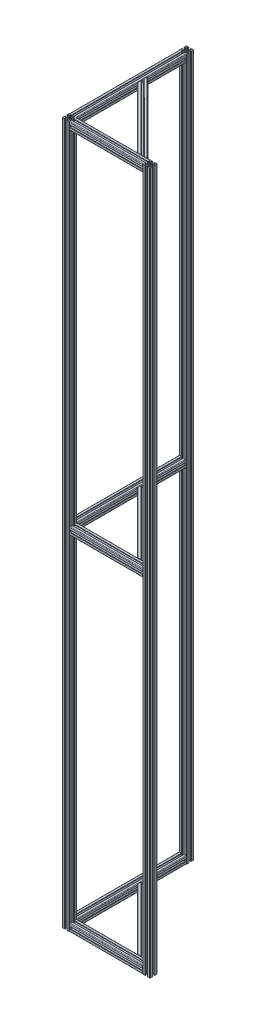
SolidWorks part; units mm, degrees
ref_plane "Front Plane" through (0, 0, 0) normal (0, 0, 1) x (1, 0, 0)
ref_plane "Top Plane" through (0, 0, 0) normal (0, 1, 0) x (1, 0, 0)
ref_plane "Right Plane" through (0, 0, 0) normal (1, 0, 0) x (0, 0, -1)
sketch "Sketch1" plane through (0, 0, 0) normal (0, 1, 0) x (1, 0, 0)
  line L0 (0, 0) -> (0, 406.4)
  line L1 (0, 0) -> (279.4, 0)
  line L2 (0, 254) -> (254, 0)
  point P6 (0, 0)
  point P7 (0, 0)
  dimension "D1" = 90
  dimension "D2" = 406.4
  dimension "D3" = 279.4
  dimension "D4" = 45
  dimension "D5" = 254
ref_plane "Plane1" through (0, 787.4, 0) normal (0, 1, 0) x (1, 0, 0)
sketch "Sketch2" plane through (0, 787.4, 0) normal (0, 1, 0) x (1, 0, 0)
  line L0 (0, 254) -> (254, 0) construction
  line L1 (0, 0) -> (0, 406.4) construction
  line L2 (0, 0) -> (279.4, 0) construction
  line L3 (0, 254) -> (254, 0)
  line L4 (0, 0) -> (0, 406.4)
  line L5 (0, 0) -> (279.4, 0)
ref_plane "Plane2" through (0, 1193.8, 0) normal (0, 1, 0) x (1, 0, 0)
sketch "Sketch3" plane through (0, 1193.8, 0) normal (0, 1, 0) x (1, 0, 0)
  line L0 (0, 254) -> (254, 0) construction
  line L1 (0, 0) -> (0, 406.4) construction
  line L2 (0, 0) -> (279.4, 0) construction
  line L3 (0, 254) -> (254, 0)
  line L4 (0, 0) -> (0, 406.4)
  line L5 (0, 0) -> (279.4, 0)
ref_plane "Plane3" through (0, 2413, 0) normal (0, 1, 0) x (1, 0, 0)
sketch "Sketch4" plane through (0, 2413, 0) normal (0, 1, 0) x (1, 0, 0)
  line L0 (0, 254) -> (254, 0) construction
  line L1 (0, 0) -> (0, 406.4) construction
  line L2 (0, 0) -> (279.4, 0) construction
  line L3 (0, 254) -> (254, 0)
  line L4 (0, 0) -> (0, 406.4)
  line L5 (0, 0) -> (279.4, 0)
sketch3d "3DSketch1"
  line L0 (0, 0, 0) -> (0, 2413, 0)
  line L1 (279.4, 0, 0) -> (279.4, 2413, 0)
  line L2 (0, 2413, -406.4) -> (0, 0, -406.4)
other "8020 1010-S(1)"
ref_plane "Plane4" through (279.4, 0, 0) normal (0, 1, 0) x (1, 0, 0)
sketch "Sketch11" plane through (279.4, 0, 0) normal (0, 1, 0) x (1, 0, 0)
  line L0 (-2.8605, -1.9692) -> (-2.2319, -1.3405)
  line L1 (-2.2319, 1.3405) -> (-2.8605, 1.9692)
  line L2 (-1.9692, 2.8605) -> (-1.3405, 2.2319)
  line L3 (1.3405, 2.2319) -> (1.9692, 2.8605)
  line L4 (2.8605, 1.9692) -> (2.2319, 1.3405)
  line L5 (2.2319, -1.3405) -> (2.8605, -1.9692)
  line L6 (1.9692, -2.8605) -> (1.3405, -2.2319)
  line L7 (-1.3405, -2.2319) -> (-1.9692, -2.8605)
  line L8 (-3.8846, 5.4471) -> (-7.1933, 8.7558)
  line L9 (1.6396, 4.5172) -> (-1.6396, 4.5172)
  line L10 (7.1933, 8.7558) -> (3.8846, 5.4471)
  line L11 (12.7, -10.5918) -> (12.7, -4.3561)
  line L12 (5.4471, 3.8846) -> (8.7558, 7.1933)
  line L13 (4.5172, -1.6396) -> (4.5172, 1.6396)
  line L14 (8.7558, -7.1933) -> (5.4471, -3.8846)
  line L15 (-10.5918, -12.7) -> (-4.3561, -12.7)
  line L16 (3.8846, -5.4471) -> (7.1933, -8.7558)
  line L17 (-1.6396, -4.5172) -> (1.6396, -4.5172)
  line L18 (-7.1933, -8.7558) -> (-3.8846, -5.4471)
  line L19 (-12.7, 10.5918) -> (-12.7, 4.3561)
  line L20 (-5.4471, -3.8846) -> (-8.7558, -7.1933)
  line L21 (-4.5172, 1.6396) -> (-4.5172, -1.6396)
  line L22 (-8.7558, 7.1933) -> (-5.4471, 3.8846)
  line L23 (-10.5918, 12.7) -> (-4.3561, 12.7)
  line L24 (-6.4749, 10.4902) -> (-4.3561, 10.4902)
  line L25 (-10.4902, 6.4749) -> (-10.4902, 4.3561)
  line L26 (-6.4749, -10.4902) -> (-4.3561, -10.4902)
  line L27 (10.4902, -6.4749) -> (10.4902, -4.3561)
  line L28 (4.3561, 12.7) -> (10.5918, 12.7)
  line L29 (4.3561, 10.4902) -> (6.4749, 10.4902)
  line L30 (-10.4902, -4.3561) -> (-10.4902, -6.4749)
  line L31 (-12.7, -4.3561) -> (-12.7, -10.5918)
  line L32 (4.3561, -10.4902) -> (6.4749, -10.4902)
  line L33 (4.3561, -12.7) -> (10.5918, -12.7)
  line L34 (12.7, 4.3561) -> (12.7, 10.5918)
  line L35 (10.4902, 4.3561) -> (10.4902, 6.4749)
  arc A0 (-2.8605, -1.9692) -> (-1.9692, -2.8605) centre (-2.4696, -2.4696) ccw
  arc A1 (-2.2319, 1.3405) -> (-2.2319, -1.3405) centre (0, 0) ccw
  arc A2 (-1.9692, 2.8605) -> (-2.8605, 1.9692) centre (-2.4696, 2.4696) ccw
  arc A3 (1.3405, 2.2319) -> (-1.3405, 2.2319) centre (0, 0) ccw
  arc A4 (2.8605, 1.9692) -> (1.9692, 2.8605) centre (2.4696, 2.4696) ccw
  arc A5 (2.2319, -1.3405) -> (2.2319, 1.3405) centre (0, 0) ccw
  arc A6 (1.9692, -2.8605) -> (2.8605, -1.9692) centre (2.4696, -2.4696) ccw
  arc A7 (-1.3405, -2.2319) -> (1.3405, -2.2319) centre (0, 0) ccw
  arc A8 (-3.8846, 5.4471) -> (-1.6396, 4.5172) centre (-1.6396, 7.6922) ccw
  arc A9 (1.6396, 4.5172) -> (3.8846, 5.4471) centre (1.6396, 7.6922) ccw
  arc A10 (5.4471, 3.8846) -> (4.5172, 1.6396) centre (7.6922, 1.6396) ccw
  arc A11 (4.5172, -1.6396) -> (5.4471, -3.8846) centre (7.6922, -1.6396) ccw
  arc A12 (3.8846, -5.4471) -> (1.6396, -4.5172) centre (1.6396, -7.6922) ccw
  arc A13 (-1.6396, -4.5172) -> (-3.8846, -5.4471) centre (-1.6396, -7.6922) ccw
  arc A14 (-5.4471, -3.8846) -> (-4.5172, -1.6396) centre (-7.6922, -1.6396) ccw
  arc A15 (-4.5172, 1.6396) -> (-5.4471, 3.8846) centre (-7.6922, 1.6396) ccw
  arc A16 (-12.7, -10.5918) -> (-10.5918, -12.7) centre (-10.5918, -10.5918) ccw
  arc A17 (10.5918, -12.7) -> (12.7, -10.5918) centre (10.5918, -10.5918) ccw
  arc A18 (12.7, 10.5918) -> (10.5918, 12.7) centre (10.5918, 10.5918) ccw
  arc A19 (-10.5918, 12.7) -> (-12.7, 10.5918) centre (-10.5918, 10.5918) ccw
  arc A20 (-8.7558, 7.1933) -> (-10.4902, 6.4749) centre (-9.4742, 6.4749) ccw
  arc A21 (-6.4749, 10.4902) -> (-7.1933, 8.7558) centre (-6.4749, 9.4742) ccw
  arc A22 (7.1933, 8.7558) -> (6.4749, 10.4902) centre (6.4749, 9.4742) ccw
  arc A23 (10.4902, 6.4749) -> (8.7558, 7.1933) centre (9.4742, 6.4749) ccw
  arc A24 (8.7558, -7.1933) -> (10.4902, -6.4749) centre (9.4742, -6.4749) ccw
  arc A25 (6.4749, -10.4902) -> (7.1933, -8.7558) centre (6.4749, -9.4742) ccw
  arc A26 (-7.1933, -8.7558) -> (-6.4749, -10.4902) centre (-6.4749, -9.4742) ccw
  arc A27 (-10.4902, -6.4749) -> (-8.7558, -7.1933) centre (-9.4742, -6.4749) ccw
  arc A28 (-4.3561, 10.4902) -> (-4.3561, 12.7) centre (-4.3561, 11.5951) ccw
  arc A29 (4.3561, 12.7) -> (4.3561, 10.4902) centre (4.3561, 11.5951) ccw
  arc A30 (-12.7, 4.3561) -> (-10.4902, 4.3561) centre (-11.5951, 4.3561) ccw
  arc A31 (-10.4902, -4.3561) -> (-12.7, -4.3561) centre (-11.5951, -4.3561) ccw
  arc A32 (-4.3561, -12.7) -> (-4.3561, -10.4902) centre (-4.3561, -11.5951) ccw
  arc A33 (4.3561, -10.4902) -> (4.3561, -12.7) centre (4.3561, -11.5951) ccw
  arc A34 (12.7, -4.3561) -> (10.4902, -4.3561) centre (11.5951, -4.3561) ccw
  arc A35 (10.4902, 4.3561) -> (12.7, 4.3561) centre (11.5951, 4.3561) ccw
  point P0 (0, 0)
other "8020 1010-S(2)"
ref_plane "Plane5" through (0, 2413, 0) normal (1, 0, 0) x (0, 0, -1)
sketch "Sketch12" plane through (0, 2413, 0) normal (1, 0, 0) x (0, 0, -1)
  line L0 (-2.8605, -1.9692) -> (-2.2319, -1.3405)
  line L1 (-2.2319, 1.3405) -> (-2.8605, 1.9692)
  line L2 (-1.9692, 2.8605) -> (-1.3405, 2.2319)
  line L3 (1.3405, 2.2319) -> (1.9692, 2.8605)
  line L4 (2.8605, 1.9692) -> (2.2319, 1.3405)
  line L5 (2.2319, -1.3405) -> (2.8605, -1.9692)
  line L6 (1.9692, -2.8605) -> (1.3405, -2.2319)
  line L7 (-1.3405, -2.2319) -> (-1.9692, -2.8605)
  line L8 (-3.8846, 5.4471) -> (-7.1933, 8.7558)
  line L9 (1.6396, 4.5172) -> (-1.6396, 4.5172)
  line L10 (7.1933, 8.7558) -> (3.8846, 5.4471)
  line L11 (12.7, -10.5918) -> (12.7, -4.3561)
  line L12 (5.4471, 3.8846) -> (8.7558, 7.1933)
  line L13 (4.5172, -1.6396) -> (4.5172, 1.6396)
  line L14 (8.7558, -7.1933) -> (5.4471, -3.8846)
  line L15 (-10.5918, -12.7) -> (-4.3561, -12.7)
  line L16 (3.8846, -5.4471) -> (7.1933, -8.7558)
  line L17 (-1.6396, -4.5172) -> (1.6396, -4.5172)
  line L18 (-7.1933, -8.7558) -> (-3.8846, -5.4471)
  line L19 (-12.7, 10.5918) -> (-12.7, 4.3561)
  line L20 (-5.4471, -3.8846) -> (-8.7558, -7.1933)
  line L21 (-4.5172, 1.6396) -> (-4.5172, -1.6396)
  line L22 (-8.7558, 7.1933) -> (-5.4471, 3.8846)
  line L23 (-10.5918, 12.7) -> (-4.3561, 12.7)
  line L24 (-6.4749, 10.4902) -> (-4.3561, 10.4902)
  line L25 (-10.4902, 6.4749) -> (-10.4902, 4.3561)
  line L26 (-6.4749, -10.4902) -> (-4.3561, -10.4902)
  line L27 (10.4902, -6.4749) -> (10.4902, -4.3561)
  line L28 (4.3561, 12.7) -> (10.5918, 12.7)
  line L29 (4.3561, 10.4902) -> (6.4749, 10.4902)
  line L30 (-10.4902, -4.3561) -> (-10.4902, -6.4749)
  line L31 (-12.7, -4.3561) -> (-12.7, -10.5918)
  line L32 (4.3561, -10.4902) -> (6.4749, -10.4902)
  line L33 (4.3561, -12.7) -> (10.5918, -12.7)
  line L34 (12.7, 4.3561) -> (12.7, 10.5918)
  line L35 (10.4902, 4.3561) -> (10.4902, 6.4749)
  arc A0 (-2.8605, -1.9692) -> (-1.9692, -2.8605) centre (-2.4696, -2.4696) ccw
  arc A1 (-2.2319, 1.3405) -> (-2.2319, -1.3405) centre (0, 0) ccw
  arc A2 (-1.9692, 2.8605) -> (-2.8605, 1.9692) centre (-2.4696, 2.4696) ccw
  arc A3 (1.3405, 2.2319) -> (-1.3405, 2.2319) centre (0, 0) ccw
  arc A4 (2.8605, 1.9692) -> (1.9692, 2.8605) centre (2.4696, 2.4696) ccw
  arc A5 (2.2319, -1.3405) -> (2.2319, 1.3405) centre (0, 0) ccw
  arc A6 (1.9692, -2.8605) -> (2.8605, -1.9692) centre (2.4696, -2.4696) ccw
  arc A7 (-1.3405, -2.2319) -> (1.3405, -2.2319) centre (0, 0) ccw
  arc A8 (-3.8846, 5.4471) -> (-1.6396, 4.5172) centre (-1.6396, 7.6922) ccw
  arc A9 (1.6396, 4.5172) -> (3.8846, 5.4471) centre (1.6396, 7.6922) ccw
  arc A10 (5.4471, 3.8846) -> (4.5172, 1.6396) centre (7.6922, 1.6396) ccw
  arc A11 (4.5172, -1.6396) -> (5.4471, -3.8846) centre (7.6922, -1.6396) ccw
  arc A12 (3.8846, -5.4471) -> (1.6396, -4.5172) centre (1.6396, -7.6922) ccw
  arc A13 (-1.6396, -4.5172) -> (-3.8846, -5.4471) centre (-1.6396, -7.6922) ccw
  arc A14 (-5.4471, -3.8846) -> (-4.5172, -1.6396) centre (-7.6922, -1.6396) ccw
  arc A15 (-4.5172, 1.6396) -> (-5.4471, 3.8846) centre (-7.6922, 1.6396) ccw
  arc A16 (-12.7, -10.5918) -> (-10.5918, -12.7) centre (-10.5918, -10.5918) ccw
  arc A17 (10.5918, -12.7) -> (12.7, -10.5918) centre (10.5918, -10.5918) ccw
  arc A18 (12.7, 10.5918) -> (10.5918, 12.7) centre (10.5918, 10.5918) ccw
  arc A19 (-10.5918, 12.7) -> (-12.7, 10.5918) centre (-10.5918, 10.5918) ccw
  arc A20 (-8.7558, 7.1933) -> (-10.4902, 6.4749) centre (-9.4742, 6.4749) ccw
  arc A21 (-6.4749, 10.4902) -> (-7.1933, 8.7558) centre (-6.4749, 9.4742) ccw
  arc A22 (7.1933, 8.7558) -> (6.4749, 10.4902) centre (6.4749, 9.4742) ccw
  arc A23 (10.4902, 6.4749) -> (8.7558, 7.1933) centre (9.4742, 6.4749) ccw
  arc A24 (8.7558, -7.1933) -> (10.4902, -6.4749) centre (9.4742, -6.4749) ccw
  arc A25 (6.4749, -10.4902) -> (7.1933, -8.7558) centre (6.4749, -9.4742) ccw
  arc A26 (-7.1933, -8.7558) -> (-6.4749, -10.4902) centre (-6.4749, -9.4742) ccw
  arc A27 (-10.4902, -6.4749) -> (-8.7558, -7.1933) centre (-9.4742, -6.4749) ccw
  arc A28 (-4.3561, 10.4902) -> (-4.3561, 12.7) centre (-4.3561, 11.5951) ccw
  arc A29 (4.3561, 12.7) -> (4.3561, 10.4902) centre (4.3561, 11.5951) ccw
  arc A30 (-12.7, 4.3561) -> (-10.4902, 4.3561) centre (-11.5951, 4.3561) ccw
  arc A31 (-10.4902, -4.3561) -> (-12.7, -4.3561) centre (-11.5951, -4.3561) ccw
  arc A32 (-4.3561, -12.7) -> (-4.3561, -10.4902) centre (-4.3561, -11.5951) ccw
  arc A33 (4.3561, -10.4902) -> (4.3561, -12.7) centre (4.3561, -11.5951) ccw
  arc A34 (12.7, -4.3561) -> (10.4902, -4.3561) centre (11.5951, -4.3561) ccw
  arc A35 (10.4902, 4.3561) -> (12.7, 4.3561) centre (11.5951, 4.3561) ccw
  point P0 (0, 0)
other "8020 1010-S(3)"
ref_plane "Plane6" through (0, 2413, 0) normal (0, 0, -1) x (-1, 0, 0)
sketch "Sketch13" plane through (0, 2413, 0) normal (0, 0, -1) x (-1, 0, 0)
  line L0 (-2.8605, -1.9692) -> (-2.2319, -1.3405)
  line L1 (-2.2319, 1.3405) -> (-2.8605, 1.9692)
  line L2 (-1.9692, 2.8605) -> (-1.3405, 2.2319)
  line L3 (1.3405, 2.2319) -> (1.9692, 2.8605)
  line L4 (2.8605, 1.9692) -> (2.2319, 1.3405)
  line L5 (2.2319, -1.3405) -> (2.8605, -1.9692)
  line L6 (1.9692, -2.8605) -> (1.3405, -2.2319)
  line L7 (-1.3405, -2.2319) -> (-1.9692, -2.8605)
  line L8 (-3.8846, 5.4471) -> (-7.1933, 8.7558)
  line L9 (1.6396, 4.5172) -> (-1.6396, 4.5172)
  line L10 (7.1933, 8.7558) -> (3.8846, 5.4471)
  line L11 (12.7, -10.5918) -> (12.7, -4.3561)
  line L12 (5.4471, 3.8846) -> (8.7558, 7.1933)
  line L13 (4.5172, -1.6396) -> (4.5172, 1.6396)
  line L14 (8.7558, -7.1933) -> (5.4471, -3.8846)
  line L15 (-10.5918, -12.7) -> (-4.3561, -12.7)
  line L16 (3.8846, -5.4471) -> (7.1933, -8.7558)
  line L17 (-1.6396, -4.5172) -> (1.6396, -4.5172)
  line L18 (-7.1933, -8.7558) -> (-3.8846, -5.4471)
  line L19 (-12.7, 10.5918) -> (-12.7, 4.3561)
  line L20 (-5.4471, -3.8846) -> (-8.7558, -7.1933)
  line L21 (-4.5172, 1.6396) -> (-4.5172, -1.6396)
  line L22 (-8.7558, 7.1933) -> (-5.4471, 3.8846)
  line L23 (-10.5918, 12.7) -> (-4.3561, 12.7)
  line L24 (-6.4749, 10.4902) -> (-4.3561, 10.4902)
  line L25 (-10.4902, 6.4749) -> (-10.4902, 4.3561)
  line L26 (-6.4749, -10.4902) -> (-4.3561, -10.4902)
  line L27 (10.4902, -6.4749) -> (10.4902, -4.3561)
  line L28 (4.3561, 12.7) -> (10.5918, 12.7)
  line L29 (4.3561, 10.4902) -> (6.4749, 10.4902)
  line L30 (-10.4902, -4.3561) -> (-10.4902, -6.4749)
  line L31 (-12.7, -4.3561) -> (-12.7, -10.5918)
  line L32 (4.3561, -10.4902) -> (6.4749, -10.4902)
  line L33 (4.3561, -12.7) -> (10.5918, -12.7)
  line L34 (12.7, 4.3561) -> (12.7, 10.5918)
  line L35 (10.4902, 4.3561) -> (10.4902, 6.4749)
  arc A0 (-2.8605, -1.9692) -> (-1.9692, -2.8605) centre (-2.4696, -2.4696) ccw
  arc A1 (-2.2319, 1.3405) -> (-2.2319, -1.3405) centre (0, 0) ccw
  arc A2 (-1.9692, 2.8605) -> (-2.8605, 1.9692) centre (-2.4696, 2.4696) ccw
  arc A3 (1.3405, 2.2319) -> (-1.3405, 2.2319) centre (0, 0) ccw
  arc A4 (2.8605, 1.9692) -> (1.9692, 2.8605) centre (2.4696, 2.4696) ccw
  arc A5 (2.2319, -1.3405) -> (2.2319, 1.3405) centre (0, 0) ccw
  arc A6 (1.9692, -2.8605) -> (2.8605, -1.9692) centre (2.4696, -2.4696) ccw
  arc A7 (-1.3405, -2.2319) -> (1.3405, -2.2319) centre (0, 0) ccw
  arc A8 (-3.8846, 5.4471) -> (-1.6396, 4.5172) centre (-1.6396, 7.6922) ccw
  arc A9 (1.6396, 4.5172) -> (3.8846, 5.4471) centre (1.6396, 7.6922) ccw
  arc A10 (5.4471, 3.8846) -> (4.5172, 1.6396) centre (7.6922, 1.6396) ccw
  arc A11 (4.5172, -1.6396) -> (5.4471, -3.8846) centre (7.6922, -1.6396) ccw
  arc A12 (3.8846, -5.4471) -> (1.6396, -4.5172) centre (1.6396, -7.6922) ccw
  arc A13 (-1.6396, -4.5172) -> (-3.8846, -5.4471) centre (-1.6396, -7.6922) ccw
  arc A14 (-5.4471, -3.8846) -> (-4.5172, -1.6396) centre (-7.6922, -1.6396) ccw
  arc A15 (-4.5172, 1.6396) -> (-5.4471, 3.8846) centre (-7.6922, 1.6396) ccw
  arc A16 (-12.7, -10.5918) -> (-10.5918, -12.7) centre (-10.5918, -10.5918) ccw
  arc A17 (10.5918, -12.7) -> (12.7, -10.5918) centre (10.5918, -10.5918) ccw
  arc A18 (12.7, 10.5918) -> (10.5918, 12.7) centre (10.5918, 10.5918) ccw
  arc A19 (-10.5918, 12.7) -> (-12.7, 10.5918) centre (-10.5918, 10.5918) ccw
  arc A20 (-8.7558, 7.1933) -> (-10.4902, 6.4749) centre (-9.4742, 6.4749) ccw
  arc A21 (-6.4749, 10.4902) -> (-7.1933, 8.7558) centre (-6.4749, 9.4742) ccw
  arc A22 (7.1933, 8.7558) -> (6.4749, 10.4902) centre (6.4749, 9.4742) ccw
  arc A23 (10.4902, 6.4749) -> (8.7558, 7.1933) centre (9.4742, 6.4749) ccw
  arc A24 (8.7558, -7.1933) -> (10.4902, -6.4749) centre (9.4742, -6.4749) ccw
  arc A25 (6.4749, -10.4902) -> (7.1933, -8.7558) centre (6.4749, -9.4742) ccw
  arc A26 (-7.1933, -8.7558) -> (-6.4749, -10.4902) centre (-6.4749, -9.4742) ccw
  arc A27 (-10.4902, -6.4749) -> (-8.7558, -7.1933) centre (-9.4742, -6.4749) ccw
  arc A28 (-4.3561, 10.4902) -> (-4.3561, 12.7) centre (-4.3561, 11.5951) ccw
  arc A29 (4.3561, 12.7) -> (4.3561, 10.4902) centre (4.3561, 11.5951) ccw
  arc A30 (-12.7, 4.3561) -> (-10.4902, 4.3561) centre (-11.5951, 4.3561) ccw
  arc A31 (-10.4902, -4.3561) -> (-12.7, -4.3561) centre (-11.5951, -4.3561) ccw
  arc A32 (-4.3561, -12.7) -> (-4.3561, -10.4902) centre (-4.3561, -11.5951) ccw
  arc A33 (4.3561, -10.4902) -> (4.3561, -12.7) centre (4.3561, -11.5951) ccw
  arc A34 (12.7, -4.3561) -> (10.4902, -4.3561) centre (11.5951, -4.3561) ccw
  arc A35 (10.4902, 4.3561) -> (12.7, 4.3561) centre (11.5951, 4.3561) ccw
  point P0 (0, 0)
other "8020 1010-S(4)"
ref_plane "Plane7" through (0, 2413, -254) normal (0.7071, 0, 0.7071) x (0.7071, 0, -0.7071)
sketch "Sketch14" plane through (0, 2413, -254) normal (0.7071, 0, 0.7071) x (0.7071, 0, -0.7071)
  line L0 (-2.8605, -1.9692) -> (-2.2319, -1.3405)
  line L1 (-2.2319, 1.3405) -> (-2.8605, 1.9692)
  line L2 (-1.9692, 2.8605) -> (-1.3405, 2.2319)
  line L3 (1.3405, 2.2319) -> (1.9692, 2.8605)
  line L4 (2.8605, 1.9692) -> (2.2319, 1.3405)
  line L5 (2.2319, -1.3405) -> (2.8605, -1.9692)
  line L6 (1.9692, -2.8605) -> (1.3405, -2.2319)
  line L7 (-1.3405, -2.2319) -> (-1.9692, -2.8605)
  line L8 (-3.8846, 5.4471) -> (-7.1933, 8.7558)
  line L9 (1.6396, 4.5172) -> (-1.6396, 4.5172)
  line L10 (7.1933, 8.7558) -> (3.8846, 5.4471)
  line L11 (12.7, -10.5918) -> (12.7, -4.3561)
  line L12 (5.4471, 3.8846) -> (8.7558, 7.1933)
  line L13 (4.5172, -1.6396) -> (4.5172, 1.6396)
  line L14 (8.7558, -7.1933) -> (5.4471, -3.8846)
  line L15 (-10.5918, -12.7) -> (-4.3561, -12.7)
  line L16 (3.8846, -5.4471) -> (7.1933, -8.7558)
  line L17 (-1.6396, -4.5172) -> (1.6396, -4.5172)
  line L18 (-7.1933, -8.7558) -> (-3.8846, -5.4471)
  line L19 (-12.7, 10.5918) -> (-12.7, 4.3561)
  line L20 (-5.4471, -3.8846) -> (-8.7558, -7.1933)
  line L21 (-4.5172, 1.6396) -> (-4.5172, -1.6396)
  line L22 (-8.7558, 7.1933) -> (-5.4471, 3.8846)
  line L23 (-10.5918, 12.7) -> (-4.3561, 12.7)
  line L24 (-6.4749, 10.4902) -> (-4.3561, 10.4902)
  line L25 (-10.4902, 6.4749) -> (-10.4902, 4.3561)
  line L26 (-6.4749, -10.4902) -> (-4.3561, -10.4902)
  line L27 (10.4902, -6.4749) -> (10.4902, -4.3561)
  line L28 (4.3561, 12.7) -> (10.5918, 12.7)
  line L29 (4.3561, 10.4902) -> (6.4749, 10.4902)
  line L30 (-10.4902, -4.3561) -> (-10.4902, -6.4749)
  line L31 (-12.7, -4.3561) -> (-12.7, -10.5918)
  line L32 (4.3561, -10.4902) -> (6.4749, -10.4902)
  line L33 (4.3561, -12.7) -> (10.5918, -12.7)
  line L34 (12.7, 4.3561) -> (12.7, 10.5918)
  line L35 (10.4902, 4.3561) -> (10.4902, 6.4749)
  arc A0 (-2.8605, -1.9692) -> (-1.9692, -2.8605) centre (-2.4696, -2.4696) ccw
  arc A1 (-2.2319, 1.3405) -> (-2.2319, -1.3405) centre (0, 0) ccw
  arc A2 (-1.9692, 2.8605) -> (-2.8605, 1.9692) centre (-2.4696, 2.4696) ccw
  arc A3 (1.3405, 2.2319) -> (-1.3405, 2.2319) centre (0, 0) ccw
  arc A4 (2.8605, 1.9692) -> (1.9692, 2.8605) centre (2.4696, 2.4696) ccw
  arc A5 (2.2319, -1.3405) -> (2.2319, 1.3405) centre (0, 0) ccw
  arc A6 (1.9692, -2.8605) -> (2.8605, -1.9692) centre (2.4696, -2.4696) ccw
  arc A7 (-1.3405, -2.2319) -> (1.3405, -2.2319) centre (0, 0) ccw
  arc A8 (-3.8846, 5.4471) -> (-1.6396, 4.5172) centre (-1.6396, 7.6922) ccw
  arc A9 (1.6396, 4.5172) -> (3.8846, 5.4471) centre (1.6396, 7.6922) ccw
  arc A10 (5.4471, 3.8846) -> (4.5172, 1.6396) centre (7.6922, 1.6396) ccw
  arc A11 (4.5172, -1.6396) -> (5.4471, -3.8846) centre (7.6922, -1.6396) ccw
  arc A12 (3.8846, -5.4471) -> (1.6396, -4.5172) centre (1.6396, -7.6922) ccw
  arc A13 (-1.6396, -4.5172) -> (-3.8846, -5.4471) centre (-1.6396, -7.6922) ccw
  arc A14 (-5.4471, -3.8846) -> (-4.5172, -1.6396) centre (-7.6922, -1.6396) ccw
  arc A15 (-4.5172, 1.6396) -> (-5.4471, 3.8846) centre (-7.6922, 1.6396) ccw
  arc A16 (-12.7, -10.5918) -> (-10.5918, -12.7) centre (-10.5918, -10.5918) ccw
  arc A17 (10.5918, -12.7) -> (12.7, -10.5918) centre (10.5918, -10.5918) ccw
  arc A18 (12.7, 10.5918) -> (10.5918, 12.7) centre (10.5918, 10.5918) ccw
  arc A19 (-10.5918, 12.7) -> (-12.7, 10.5918) centre (-10.5918, 10.5918) ccw
  arc A20 (-8.7558, 7.1933) -> (-10.4902, 6.4749) centre (-9.4742, 6.4749) ccw
  arc A21 (-6.4749, 10.4902) -> (-7.1933, 8.7558) centre (-6.4749, 9.4742) ccw
  arc A22 (7.1933, 8.7558) -> (6.4749, 10.4902) centre (6.4749, 9.4742) ccw
  arc A23 (10.4902, 6.4749) -> (8.7558, 7.1933) centre (9.4742, 6.4749) ccw
  arc A24 (8.7558, -7.1933) -> (10.4902, -6.4749) centre (9.4742, -6.4749) ccw
  arc A25 (6.4749, -10.4902) -> (7.1933, -8.7558) centre (6.4749, -9.4742) ccw
  arc A26 (-7.1933, -8.7558) -> (-6.4749, -10.4902) centre (-6.4749, -9.4742) ccw
  arc A27 (-10.4902, -6.4749) -> (-8.7558, -7.1933) centre (-9.4742, -6.4749) ccw
  arc A28 (-4.3561, 10.4902) -> (-4.3561, 12.7) centre (-4.3561, 11.5951) ccw
  arc A29 (4.3561, 12.7) -> (4.3561, 10.4902) centre (4.3561, 11.5951) ccw
  arc A30 (-12.7, 4.3561) -> (-10.4902, 4.3561) centre (-11.5951, 4.3561) ccw
  arc A31 (-10.4902, -4.3561) -> (-12.7, -4.3561) centre (-11.5951, -4.3561) ccw
  arc A32 (-4.3561, -12.7) -> (-4.3561, -10.4902) centre (-4.3561, -11.5951) ccw
  arc A33 (4.3561, -10.4902) -> (4.3561, -12.7) centre (4.3561, -11.5951) ccw
  arc A34 (12.7, -4.3561) -> (10.4902, -4.3561) centre (11.5951, -4.3561) ccw
  arc A35 (10.4902, 4.3561) -> (12.7, 4.3561) centre (11.5951, 4.3561) ccw
  point P0 (0, 0)
other "Trim/Extend3"
other "Trim/Extend4"
other "Trim/Extend7"
other "Trim/Extend8"
